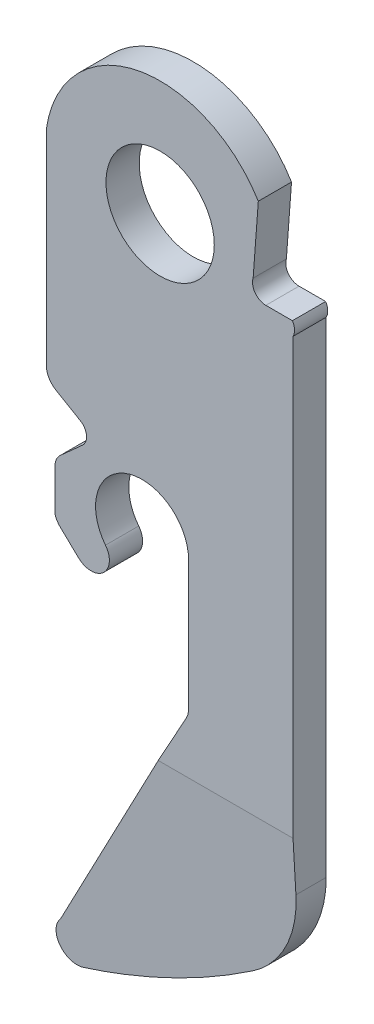
SolidWorks part; units mm, degrees
material "Plain Carbon Steel"
ref_plane "Front Plane" through (0, 0, 0) normal (0, 0, 1) x (1, 0, 0)
ref_plane "Top Plane" through (0, 0, 0) normal (0, 1, 0) x (1, 0, 0)
ref_plane "Right Plane" through (0, 0, 0) normal (1, 0, 0) x (0, 0, -1)
sketch "Sketch1" plane through (0, 0, 0) normal (0, 0, 1) x (1, 0, 0)
  line L0 (20.2608, 45.5867) -> (101.3038, 45.5867) construction
  line L1 (70.3307, 59.1391) -> (70.3307, 40.5971)
  line L2 (60.899, 61.2727) -> (60.899, 53.0431)
  line L3 (69.0035, 62.9491) -> (68.8067, 60.3075)
  line L4 (69.2913, 59.6471) -> (70.3073, 59.6471)
  line L5 (60.899, 53.0431) -> (62.2027, 52.2811)
  line L6 (62.2811, 51.5125) -> (61.4407, 50.7571)
  line L7 (61.2302, 50.2848) -> (61.2302, 48.7251)
  line L8 (61.4407, 48.3695) -> (62.1332, 47.7091)
  line L9 (66.3398, 49.7411) -> (66.3398, 44.6611)
  line L10 (66.3398, 44.6245) -> (61.0058, 34.9725)
  line L12 (66.3398, 44.6611) -> (66.3398, 44.6245)
  arc A1 (68.8067, 60.3075) -> (69.2913, 59.6471) centre (69.2913, 60.1551) ccw
  arc A2 (70.3307, 59.1391) -> (70.3073, 59.6471) centre (69.8797, 59.3729) ccw
  arc A4 (62.2811, 51.5125) -> (62.2027, 52.2811) centre (61.9614, 51.8682) ccw
  arc A5 (61.4407, 50.7571) -> (61.2302, 50.2848) centre (61.8652, 50.2848) ccw
  arc A6 (61.2302, 48.7251) -> (61.4407, 48.3695) centre (61.9666, 48.9209) ccw
  arc A7 (62.1332, 47.7091) -> (63.1628, 48.6438) centre (62.6143, 48.2136) ccw
  arc A8 (66.3398, 49.7411) -> (63.1628, 48.6438) centre (64.5618, 49.7411) ccw
  arc A10 (61.0058, 34.9725) -> (61.8107, 33.7391) centre (61.5722, 34.4628) ccw
  arc A11 (68.4622, 37.0411) -> (70.3307, 40.5971) centre (66.0127, 40.5971) ccw
  arc A12 (61.8107, 33.7391) -> (68.4622, 37.0411) centre (53.6212, 58.5863) ccw
  arc A13 (69.0035, 62.9491) -> (60.899, 61.2727) centre (65.2507, 60.6631) ccw
  point P3 (0, 0)
  point P5 (0, 0)
  point P17 (0, 0)
  point P18 (65.3322, 59.3132)
  point P22 (0, 0)
  point P25 (0, 0)
  point P28 (0, 0)
  point P32 (0, 0)
  point P35 (0, 0)
  point P38 (0, 0)
  point P39 (0, 0)
  point P40 (0, 0)
  dimension "D2" = 4.3942
  dimension "D4" = 7.62
  dimension "D6" = 3.556
  dimension "D7" = 0.3556
  dimension "D8" = 0.508
  dimension "D9" = 1.016
  dimension "D10" = 0.6971
  dimension "D11" = 0.4783
  dimension "D12" = 1.016
  dimension "D13" = 0.508
  dimension "D17" = 4.318
  dimension "D19" = 26.162
  dimension "D20" = 26.924
  dimension "D21" = 0.762
  dimension "D30" = 0.635
  dimension "D33" = 0.762
  dimension "D37" = 1.778
  dimension "D3" = 8.2296
  dimension "D5" = 2.286
  dimension "D14" = 18.542
  dimension "D15" = 1.524
  dimension "D16" = 5.08
  dimension "D18" = 23.622
  dimension "D22" = 9.652
  dimension "D23" = 5.334
  dimension "D24" = 16.002
  dimension "D25" = 10.922
  dimension "D26" = 8.382
  dimension "D27" = 3.048
  dimension "D28" = 3.81
  dimension "D29" = 9.906
  dimension "D31" = 11.938
  dimension "D32" = 1.5597
  dimension "D34" = 12.2936
  dimension "D35" = 12.954
  dimension "D36" = 3.81
extrude "Boss-Extrude1" add sketch "Sketch1" along normal blind 1.27
sketch "Sketch2" plane through (0, 0, 1.27) normal (0, 0, 1) x (1, 0, 0)
  circle A0 centre (65.2507, 60.6631) radius 2.0701
  dimension "D1" = 4.1402
extrude "Cut-Extrude1" cut sketch "Sketch2" against normal through all
fillet "Fillet1" radius 0.762 2 edges at (60.899, 53.0431, 0.635) (66.3398, 44.6245, 0.635)
sketch "Sketch3" plane through (70.3307, 0, 0) normal (1, 0, 0) x (0, 0, -1)
  line L8 (-1.27, 33.7008) -> (-0.762, 33.7008)
  line L9 (-1.27, 33.7008) -> (0, 33.7008) construction
  line L10 (-0.762, 33.7008) -> (-1.27, 42.5256)
  line L11 (-1.27, 40.5971) -> (-1.27, 59.1391) construction
  line L12 (-1.27, 42.5256) -> (-1.27, 33.7008)
  line L13 (0, 33.7391) -> (0, 37.0411) construction
  dimension "D1" = 0.762
  dimension "D2" = 3.295
extrude "Cut-Extrude2" cut sketch "Sketch3" against normal through all
